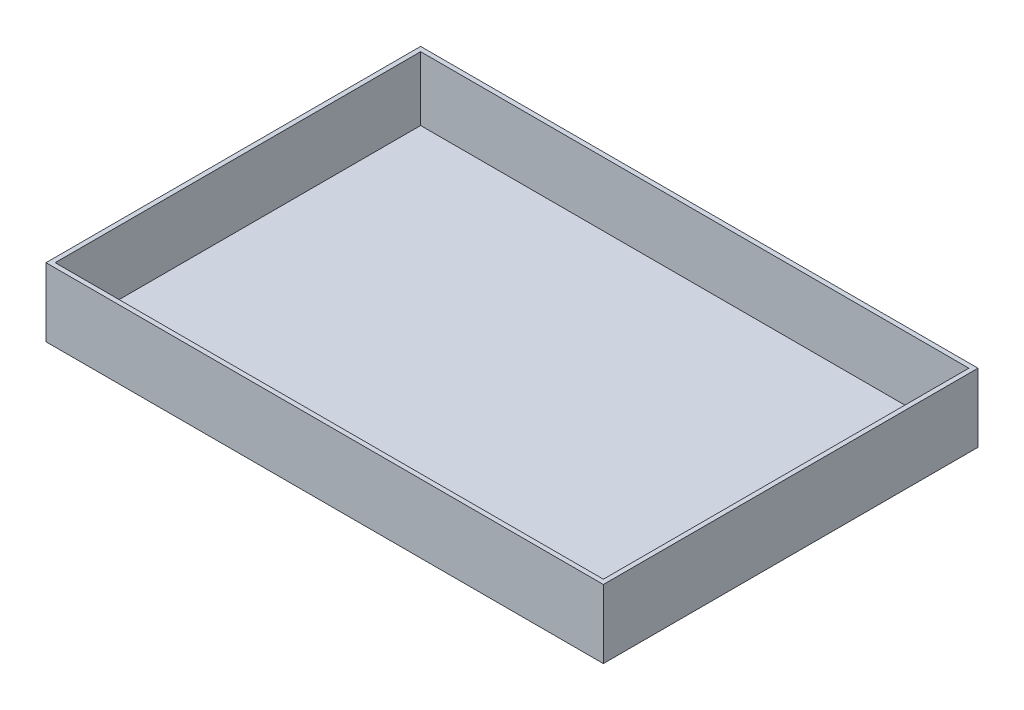
SolidWorks part; units mm, degrees
ref_plane "正面" through (0, 0, 0) normal (0, 0, 1) x (1, 0, 0)
ref_plane "平面" through (0, 0, 0) normal (0, 1, 0) x (1, 0, 0)
ref_plane "右側面" through (0, 0, 0) normal (1, 0, 0) x (0, 0, -1)
sketch "ｽｹｯﾁ1" plane through (0, 0, 0) normal (0, 1, 0) x (1, 0, 0)
  line L1 (-305, 205) -> (305, 205)
  line L2 (-305, 205) -> (-305, -205)
  line L3 (-305, -205) -> (305, -205)
  line L4 (305, 205) -> (305, -205)
  line L5 (-305, 205) -> (305, -205) construction
  line L6 (-305, -205) -> (305, 205) construction
  point P0 (0, 0)
  dimension "D1" = 410
  dimension "600" = 610
extrude "ﾎﾞｽ - 押し出し1" add sketch "ｽｹｯﾁ1" along normal blind 75
shell "ｼｪﾙ1" thickness 5 removed face at (0, 75, 0)
